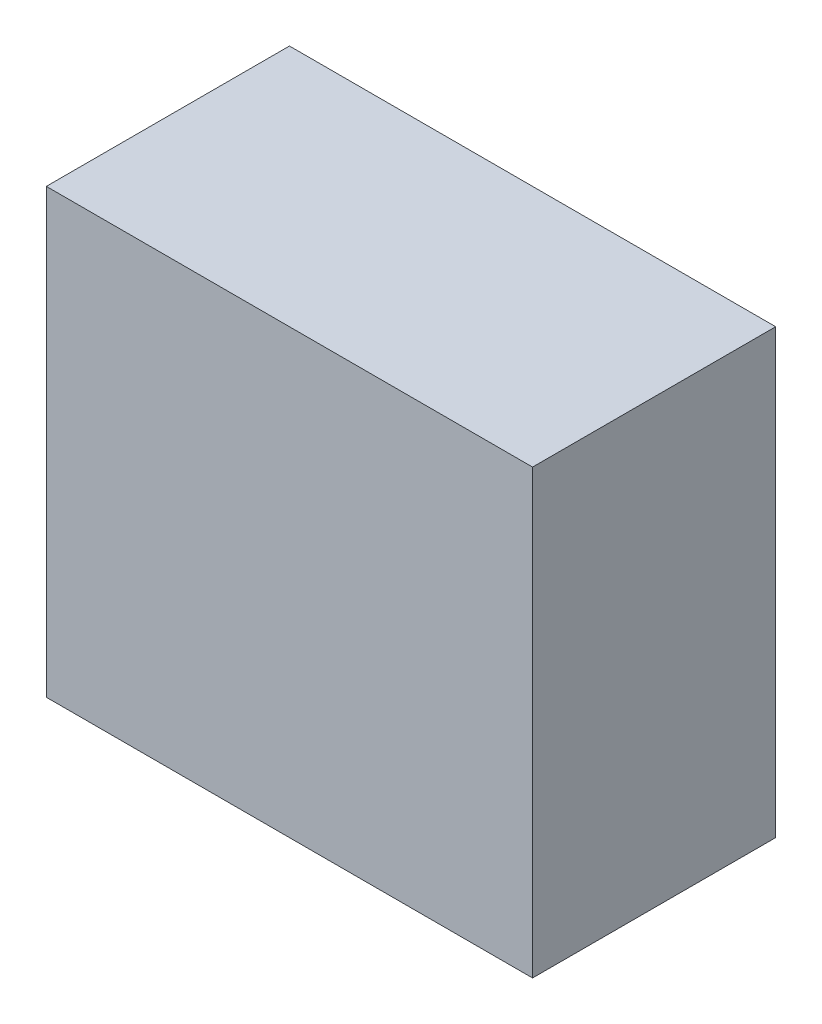
SolidWorks part; units mm, degrees
ref_plane "Front Plane" through (0, 0, 0) normal (0, 0, 1) x (1, 0, 0)
ref_plane "Top Plane" through (0, 0, 0) normal (0, 1, 0) x (1, 0, 0)
ref_plane "Right Plane" through (0, 0, 0) normal (1, 0, 0) x (0, 0, -1)
sketch "Sketch1" plane through (0, 0, 0) normal (0, 1, 0) x (1, 0, 0)
  line L1 (-25.4, 12.7) -> (25.4, 12.7)
  line L2 (-25.4, 12.7) -> (-25.4, -12.7)
  line L3 (-25.4, -12.7) -> (25.4, -12.7)
  line L4 (25.4, 12.7) -> (25.4, -12.7)
  line L5 (-25.4, 12.7) -> (25.4, -12.7) construction
  line L6 (-25.4, -12.7) -> (25.4, 12.7) construction
  point P0 (0, 0)
  dimension "D1" = 50.8
  dimension "D2" = 25.4
extrude "Boss-Extrude1" add sketch "Sketch1" along normal blind 46.23
